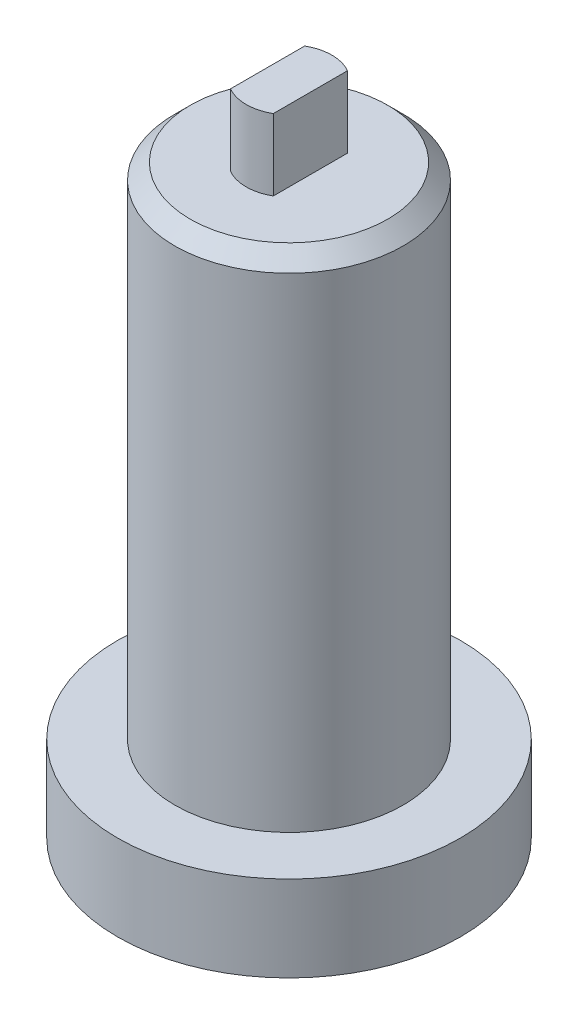
SolidWorks part; units mm, degrees
ref_plane "前视基准面" through (0, 0, 0) normal (0, 0, 1) x (1, 0, 0)
ref_plane "上视基准面" through (0, 0, 0) normal (0, 1, 0) x (1, 0, 0)
ref_plane "右视基准面" through (0, 0, 0) normal (1, 0, 0) x (0, 0, -1)
sketch "草图1" plane through (0, 0, 0) normal (0, 0, 1) x (1, 0, 0)
  line L0 (0, 46) -> (3, 46)
  line L1 (3, 46) -> (3, 41)
  line L2 (3, 41) -> (6.9175, 41)
  line L3 (6.9175, 41) -> (8, 39.9175)
  line L4 (8, 39.9175) -> (8, 6)
  line L5 (8, 6) -> (12, 6)
  line L6 (12, 6) -> (12, 0)
  line L7 (12, 0) -> (0, 0)
  line L8 (0, 0) -> (0, 46)
  line L9 (0, 0) -> (0, 46) construction
revolve "旋转1" add sketch "草图1" angle 360 about L9 reverse direction yes
cosmetic thread "装饰螺纹线1" parameters "D1"=23, "D2"=13.835
sketch "草图2" plane through (0, 0, 0) normal (0, 0, 1) x (1, 0, 0)
  line L0 (-3, 41) -> (-1.5, 41)
  line L1 (-1.5, 41) -> (-1.5, 46)
  line L2 (-1.5, 46) -> (1.5, 46)
  line L3 (1.5, 46) -> (1.5, 41)
  line L4 (1.5, 41) -> (3, 41)
  line L5 (3, 41) -> (3, 49)
  line L6 (3, 49) -> (-3, 49)
  line L7 (-3, 49) -> (-3, 41)
extrude "切除-拉伸1" cut sketch "草图2" along normal blind 16 and the other way blind 16
ref_plane "基准面4" through (0, 6, 0) normal (0, 1, 0) x (1, 0, 0)
ref_plane "基准面5" through (0, 46, 0) normal (0, 1, 0) x (1, 0, 0)
ref_plane "piston_to_body XY" through (0, 6, 0) normal (0, 1, 0) x (1, 0, 0)
ref_plane "piston_to_body XZ" through (0, 0, 0) normal (0, 0, 1) x (1, 0, 0)
ref_plane "piston_to_body YZ" through (0, 0, 0) normal (1, 0, 0) x (0, 0, -1)
ref_axis "piston_to_body X" through (-80.9, 6, 0) along (1, 0, 0)
ref_axis "piston_to_body Y" through (0, 6, 50) along (0, 0, -1)
ref_axis "piston_to_body Z" through (0, 50, 0) along (0, -1, 0)
sketch3d "piston_to_body"
  point P0 (0, 6, 0)
ref_plane "handle_to_piston XY" through (0, 46, 0) normal (0, 1, 0) x (1, 0, 0)
ref_plane "handle_to_piston XZ" through (0, 0, 0) normal (0, 0, 1) x (1, 0, 0)
ref_plane "handle_to_piston YZ" through (0, 0, 0) normal (1, 0, 0) x (0, 0, -1)
ref_axis "handle_to_piston X" through (-80.9, 46, 0) along (1, 0, 0)
ref_axis "handle_to_piston Y" through (0, 46, 50) along (0, 0, -1)
ref_axis "handle_to_piston Z" through (0, 50, 0) along (0, -1, 0)
sketch3d "handle_to_piston"
  point P0 (0, 46, 0)
